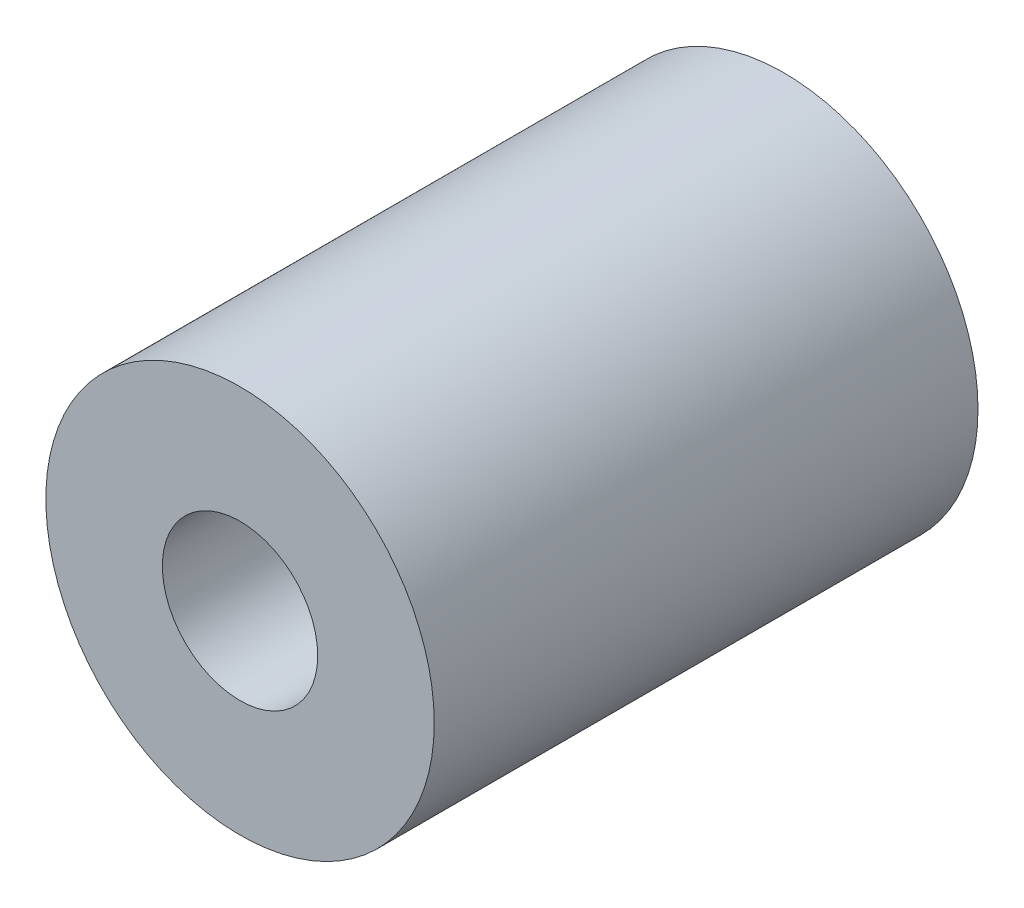
SolidWorks part; units mm, degrees
other "Title Block Table1"
other "DetailItem1"
material "PA Type 6 - Black"
ref_plane "Front Plane" through (0, 0, 0) normal (0, 0, 1) x (1, 0, 0)
ref_plane "Top Plane" through (0, 0, 0) normal (0, 1, 0) x (1, 0, 0)
ref_plane "Right Plane" through (0, 0, 0) normal (1, 0, 0) x (0, 0, -1)
ref_axis "X-Axis" through (-11, 0, 0) along (1, 0, 0)
ref_axis "Y-Axis" through (0, 11, 0) along (0, -1, 0)
ref_axis "Z-Axis" through (0, 0, -17.6) along (0, 0, 1)
sketch "Sketch1" plane through (0, 0, 0) normal (0, 0, 1) x (1, 0, 0)
  circle A0 centre (0, 0) radius 5
  circle A1 centre (0, 0) radius 2
  dimension "D1" = 10
  dimension "D2" = 4
extrude "Boss-Extrude1" add sketch "Sketch1" along normal mid plane 14
